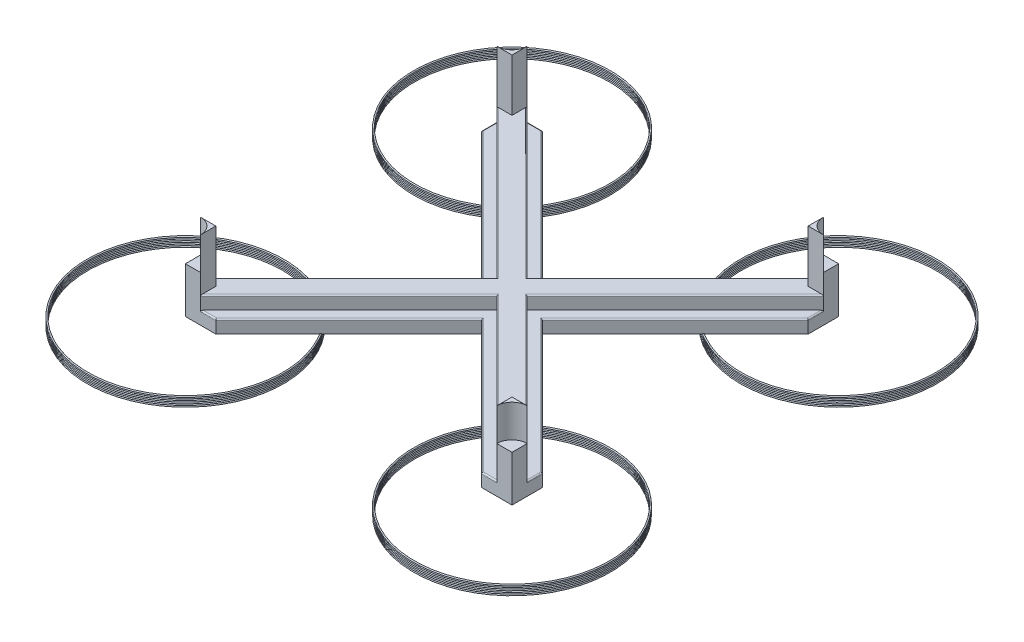
SolidWorks part; units mm, degrees
material "ABS"
ref_plane "Front Plane" through (0, 0, 0) normal (0, 0, 1) x (1, 0, 0)
ref_plane "Top Plane" through (0, 0, 0) normal (0, 1, 0) x (1, 0, 0)
ref_plane "Right Plane" through (0, 0, 0) normal (1, 0, 0) x (0, 0, -1)
sketch "Sketch1" plane through (0, 0, 0) normal (0, 1, 0) x (1, 0, 0)
  line L0 (-11.8367, 0) -> (-63.5, 51.6633)
  line L1 (-63.5, -63.5) -> (-51.6633, -63.5)
  line L2 (-63.5, -63.5) -> (-63.5, -51.6633)
  line L3 (-63.5, 63.5) -> (-51.6633, 63.5)
  line L4 (63.5, -63.5) -> (63.5, -51.6633)
  line L5 (-63.5, -63.5) -> (63.5, 63.5) construction
  line L6 (-63.5, 63.5) -> (63.5, -63.5) construction
  line L7 (0, -11.8367) -> (51.6633, -63.5)
  line L8 (0, 11.8367) -> (-51.6633, 63.5)
  line L9 (11.8367, 0) -> (63.5, -51.6633)
  line L12 (-63.5, -51.6633) -> (-11.8367, 0)
  line L13 (63.5, 51.6633) -> (11.8367, 0)
  line L16 (51.6633, 63.5) -> (63.5, 63.5)
  line L17 (63.5, 51.6633) -> (63.5, 63.5)
  line L18 (-63.5, 51.6633) -> (-63.5, 63.5)
  line L19 (51.6633, -63.5) -> (63.5, -63.5)
  line L20 (0, 11.8367) -> (51.6633, 63.5)
  line L21 (0, -11.8367) -> (-51.6633, -63.5)
  point P0 (0, 0)
extrude "Boss-Extrude1" add sketch "Sketch1" along normal blind 5.08
ref_plane "Plane3" through (0, 0, 0) normal (0, 0, -1) x (-1, 0, 0)
ref_plane "Plane1" through (0, 0, 0) normal (0.7071, 0, -0.7071) x (-0.7071, 0, -0.7071)
ref_plane "Plane2" through (0, 0, 0) normal (1, 0, 0) x (0, 0, -1)
sketch "Sketch3" plane through (0, 5.08, 0) normal (0, 1, 0) x (1, 0, 0)
  line L0 (-63.5, -63.5) -> (63.5, 63.5) construction
  line L1 (-63.5, -63.5) -> (-57.5816, -63.5)
  line L2 (-63.5, -63.5) -> (-63.5, -57.5816)
  line L3 (-63.5, -57.5816) -> (-57.5816, -57.5816)
  line L4 (-57.5816, -63.5) -> (-57.5816, -57.5816)
  line L5 (-63.5, -63.5) -> (-63.5, -51.6633) construction
  line L8 (1.9757, -1.9757) -> (-1.9757, 1.9757) construction
  line L9 (57.5816, 63.5) -> (57.5816, 57.5816)
  line L10 (63.5, 57.5816) -> (57.5816, 57.5816)
  line L11 (63.5, 63.5) -> (63.5, 57.5816)
  line L12 (63.5, 63.5) -> (57.5816, 63.5)
  line L13 (2.794, 0) -> (-2.794, 0) construction
  line L14 (-63.5, 57.5816) -> (-57.5816, 57.5816)
  line L15 (-57.5816, 63.5) -> (-57.5816, 57.5816)
  line L16 (-63.5, 63.5) -> (-57.5816, 63.5)
  line L17 (-63.5, 63.5) -> (-63.5, 57.5816)
  line L18 (0, -2.794) -> (0, 2.794) construction
  line L19 (63.5, -57.5816) -> (57.5816, -57.5816)
  line L20 (57.5816, -63.5) -> (57.5816, -57.5816)
  line L21 (63.5, -63.5) -> (57.5816, -63.5)
  line L22 (63.5, -63.5) -> (63.5, -57.5816)
extrude "Boss-Extrude2" add sketch "Sketch3" along normal blind 38.1
sketch "Sketch4" plane through (0, 0, 0) normal (0, -1, 0) x (1, 0, 0)
  circle A4 centre (-63.5, 63.5) radius 38.1
  point P12 (0, 0)
  point P14 (0, 0)
  point P21 (0, 0)
ref_plane "Plane4" through (0, 0, 0) normal (0.7071, 0, 0.7071) x (0.7071, 0, -0.7071)
sweep "Sweep11" add path "Sketch4" circular profile diameter 0.508 parameters "D3"=0.508
ref_axis "Axis1" through (0, 0, 0) along (0, 1, 0)
pattern_circular "CirPattern1" count 4 over 360 about axis through (0, 0, 0) along (0, 1, 0) of "Sweep11"
sketch "Sketch5" plane through (0, 43.18, 0) normal (0, 1, 0) x (1, 0, 0)
  circle A0 centre (63.5, -63.5) radius 5.9184
extrude "Cut-Extrude1" cut sketch "Sketch5" against normal blind 25.4
pattern_circular "CirPattern2" count 4 over 360 about axis through (0, 0, 0) along (0, 1, 0) of "Cut-Extrude1" reverse direction yes
ref_plane "Plane5" through (0, -0.508, 0) normal (0, -1, 0) x (-1, 0, 0)
ref_axis "Axis2" through (-63.5, 17.78, 63.5) along (0, -1, 0)
sketch "Sketch14" plane through (0, -0.508, 0) normal (0, -1, 0) x (-1, 0, 0)
  circle A0 centre (63.5, -63.5) radius 38.1
sweep "Sweep13" add path "Sketch14" circular profile diameter 0.508 parameters "D3"=0.508
pattern_circular "CirPattern8" count 4 over 360 about axis through (0, 0, 0) along (0, 1, 0) of bodies 109
pattern_linear "LPattern16" count 6 spacing 0.5588 along (0, -1, 0) of bodies 121 120 122 109
sketch "Sketch84" plane through (0, 5.08, 0) normal (0, 1, 0) x (1, 0, 0)
  line L0 (-63.5, 57.5816) -> (-5.9184, 0)
  line L1 (57.5816, 63.5) -> (0, 5.9184)
  line L2 (-57.5816, 63.5) -> (0, 5.9184)
  line L3 (63.5, 57.5816) -> (5.9184, 0)
  line L4 (5.9184, 0) -> (63.5, -57.5816)
  line L5 (-5.9184, 0) -> (-63.5, -57.5816)
  line L6 (0, -5.9184) -> (57.5816, -63.5)
  line L7 (0, -5.9184) -> (-57.5816, -63.5)
  line M1 (57.5816, -57.5816) -> (63.5, -57.5816)
  line M6 (63.5, 57.5816) -> (57.5816, 57.5816)
  line M7 (57.5816, 57.5816) -> (57.5816, 63.5)
  line M12 (-57.5816, 63.5) -> (-57.5816, 57.5816)
  line M13 (-57.5816, 57.5816) -> (-63.5, 57.5816)
  line M18 (-63.5, -57.5816) -> (-57.5816, -57.5816)
  line M19 (-57.5816, -57.5816) -> (-57.5816, -63.5)
  line M24 (57.5816, -63.5) -> (57.5816, -57.5816)
extrude "Boss-Extrude3" add sketch "Sketch84" along normal blind 5.08 contours L7 L6 L4 L3 L1 L2 L0 L5 M24 M1 M6 M7 M12 M13 M18 M19 region at (0, 5.08, 0)
fillet "Fillet1" radius 0.508 24 edges at (-54.6224, 5.08, -63.5) (-63.5, 5.08, -54.6224) (54.6224, 5.08, -63.5) (63.5, 5.08, -54.6224) (54.6224, 5.08, 63.5) (63.5, 5.08, 54.6224) (-63.5, 5.08, 54.6224) (-54.6224, 5.08, 63.5) (25.8316, 5.08, -37.6684) (-25.8316, 5.08, -37.6684) (-37.6684, 5.08, 25.8316) (-37.6684, 5.08, -25.8316) (37.6684, 5.08, 25.8316) (37.6684, 5.08, -25.8316) (25.8316, 5.08, 37.6684) (-25.8316, 5.08, 37.6684) (34.7092, 10.16, 28.7908) (34.7092, 10.16, -28.7908) (28.7908, 10.16, -34.7092) (-28.7908, 10.16, -34.7092) (-34.7092, 10.16, -28.7908) (-34.7092, 10.16, 28.7908) (28.7908, 10.16, 34.7092) (-28.7908, 10.16, 34.7092)
sketch "Sketch85" plane through (0, 43.18, 0) normal (0, 1, 0) x (1, 0, 0)
  line L1 (-63.5, -63.5) -> (70.1925, -63.5)
  line L2 (-63.5, -63.5) -> (-63.5, 70.1925)
  line L3 (-63.5, 70.1925) -> (70.1925, 70.1925)
  line L4 (70.1925, -63.5) -> (70.1925, 70.1925)
extrude "Cut-Extrude2" cut sketch "Sketch85" against normal blind 12.7
sketch "Sketch86" plane through (0, 17.78, 0) normal (0, 1, 0) x (1, 0, 0)
  line L0 (-63.5, -63.5) -> (-59.3151, -59.3151)
  line L1 (-63.5, 63.5) -> (-59.3151, 59.3151)
  line L2 (63.5, 63.5) -> (59.3151, 59.3151)
  line L3 (63.5, -63.5) -> (59.3151, -59.3151)
  circle A0 centre (-61.4075, -61.4075) radius 0.635
  circle A1 centre (-61.4075, 61.4075) radius 0.635
  circle A2 centre (61.4075, 61.4075) radius 0.635
  circle A3 centre (61.4075, -61.4075) radius 0.635
  point P2 (-61.4075, -61.4075)
  point P8 (-61.4075, 61.4075)
  point P11 (61.4075, 61.4075)
  point P14 (61.4075, -61.4075)
  point P15 (0, 0)
  point P24 (0, 0)
  dimension "D2" = 4
  dimension "D1" = 4
